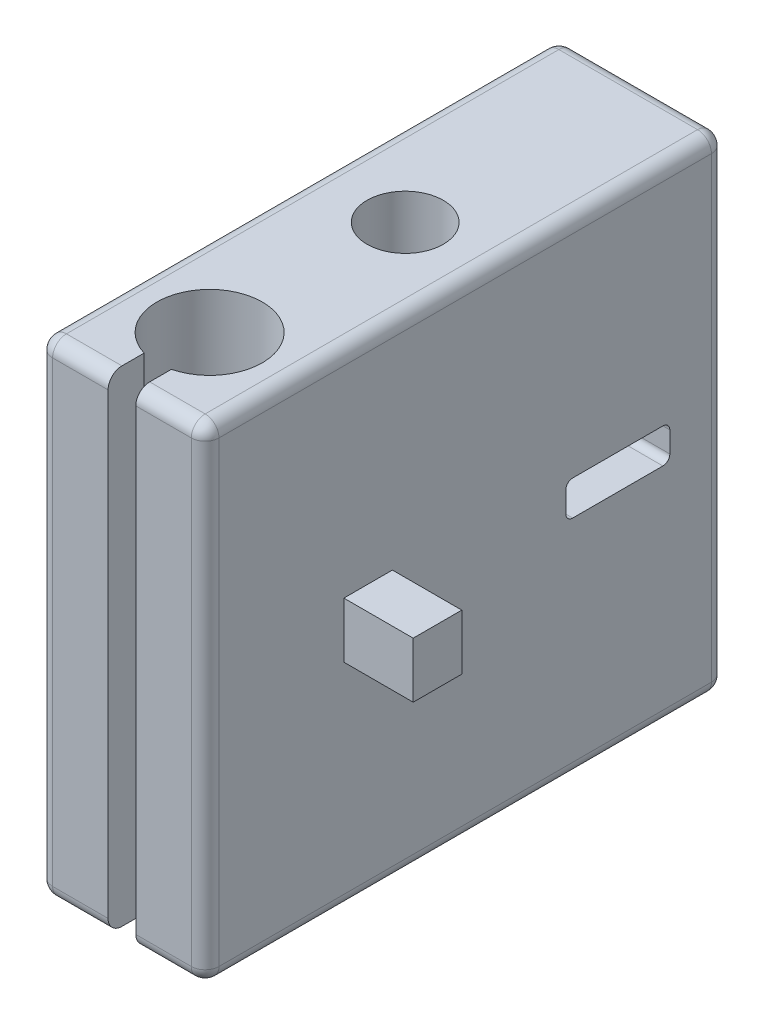
SolidWorks part; units mm, degrees
ref_plane "Front Plane" through (0, 0, 0) normal (0, 0, 1) x (1, 0, 0)
ref_plane "Top Plane" through (0, 0, 0) normal (0, 1, 0) x (1, 0, 0)
ref_plane "Right Plane" through (0, 0, 0) normal (1, 0, 0) x (0, 0, -1)
ref_plane "Plano1" through (-220, 0, 0) normal (1, 0, 0) x (0, 0, -1)
sketch "Esboço1" plane through (-220, 0, 0) normal (1, 0, 0) x (0, 0, -1)
  line L0 (-460.4999, 246.154) -> (-460.4999, 230.354) construction
  line L1 (-465.4999, 248.254) -> (-390.4999, 248.254)
  line L2 (-465.4999, 248.254) -> (-465.4999, 178.254)
  line L3 (-465.4999, 178.254) -> (-390.4999, 178.254)
  line L4 (-390.4999, 248.254) -> (-390.4999, 178.254)
  dimension "D1" = 75
  dimension "D2" = 70
  dimension "D3" = 5
extrude "Ressalto-extrusão1" add sketch "Esboço1" along normal blind 12 and the other way blind 12
sketch "Esboço3" plane through (0, 248.254, 0) normal (0, 1, 0) x (1, 0, 0)
  line L5 (-232, -465.4999) -> (-208, -465.4999) construction
  line L7 (-220, -465.4999) -> (-218, -465.4999)
  line L10 (-218, -465.4999) -> (-218, -460.3692)
  line L11 (-220, -465.4999) -> (-222, -465.4999)
  line L14 (-222, -465.4999) -> (-222, -460.292)
  arc A3 (-218, -460.3692) -> (-222, -460.292) centre (-219.8586, -452.9999) ccw
  circle A8 centre (-219.5085, -425.1499) radius 5.5
  circle A9 centre (-219.5085, -425.1499) radius 5.5
  dimension "D1" = 15.2
  dimension "D3" = 2
  dimension "D4" = 2
  dimension "D2" = 0.5
extrude "Corte-extrusão1" cut sketch "Esboço3" against normal through all
sketch "Esboço4" plane through (0, 0, 390.4999) normal (0, 0, -1) x (-1, 0, 0)
  line L0 (220, 248.254) -> (220, 178.254) construction
  line L1 (232, 248.254) -> (208, 248.254) construction
  line L2 (232, 178.254) -> (208, 178.254) construction
  circle A0 centre (219.8586, 238.254) radius 4.1
  circle A1 centre (219.8586, 188.254) radius 4.1
  dimension "D1" = 8.2
  dimension "D2" = 8.2
extrude "Corte-extrusão2" cut sketch "Esboço4" against normal blind 20
fillet "Filete1" radius 2 14 edges at (-227, 178.254, 465.4999) (-213, 178.254, 465.4999) (-213, 248.254, 465.4999) (-227, 248.254, 465.4999) (-208, 178.254, 427.9999) (-208, 248.254, 427.9999) (-208, 213.254, 465.4999) (-232, 178.254, 427.9999) (-232, 213.254, 465.4999) (-232, 248.254, 427.9999) (-220, 248.254, 390.4999) (-220, 178.254, 390.4999) (-208, 213.254, 390.4999) (-232, 213.254, 390.4999)
sketch "Esboço5" plane through (0, 0, 390.4999) normal (0, 0, -1) x (-1, 0, 0)
  line L8 (214.0299, 195.2585) -> (226.0299, 195.2486)
  line L9 (226.0299, 195.2486) -> (226.0594, 231.2486)
  line L10 (226.0594, 231.2486) -> (214.0594, 231.2584)
  line L11 (214.0594, 231.2584) -> (214.0299, 195.2585)
  line L12 (214.0299, 195.2585) -> (226.0299, 195.2486)
  line L13 (226.0299, 195.2486) -> (226.0594, 231.2486)
  line L14 (226.0594, 231.2486) -> (214.0594, 231.2584)
  line L15 (214.0594, 231.2584) -> (214.0299, 195.2585)
  dimension "D1" = 0
extrude "Corte-extrusão3" cut sketch "Esboço5" against normal blind 29
sketch "Esboço6" plane through (-232, 0, 0) normal (-1, 0, 0) x (0, 0, 1)
  line L0 (392.4999, 213.254) -> (463.4999, 213.254) construction
  line L1 (392.4999, 246.254) -> (392.4999, 180.254) construction
  line L2 (463.4999, 180.254) -> (463.4999, 246.254) construction
  line L3 (398.4999, 213.254) -> (413.4999, 213.254) construction
  line L4 (399.4999, 215.754) -> (412.4999, 215.754)
  line L5 (398.4999, 214.754) -> (398.4999, 211.754)
  line L6 (399.4999, 210.754) -> (412.4999, 210.754)
  line L7 (413.4999, 214.754) -> (413.4999, 211.754)
  arc A0 (412.4999, 215.754) -> (413.4999, 214.754) centre (412.4999, 214.754) cw
  arc A1 (412.4999, 210.754) -> (413.4999, 211.754) centre (412.4999, 211.754) ccw
  arc A2 (398.4999, 211.754) -> (399.4999, 210.754) centre (399.4999, 211.754) ccw
  arc A3 (399.4999, 215.754) -> (398.4999, 214.754) centre (399.4999, 214.754) ccw
  point P14 (413.4999, 215.754)
  point P17 (413.4999, 210.754)
  point P22 (398.4999, 215.754)
  dimension "D4" = 1
  dimension "D1" = 5
  dimension "D2" = 15
  dimension "D3" = 6
extrude "Corte-extrusão4" cut sketch "Esboço6" against normal blind 28
sketch "Esboço7" plane through (-208, 0, 0) normal (1, 0, 0) x (0, 0, -1)
  line L0 (-463.4999, 246.254) -> (-463.4999, 180.254) construction
  line L1 (-445.4999, 217.254) -> (-438.4999, 217.254)
  line L2 (-445.4999, 217.254) -> (-445.4999, 209.254)
  line L3 (-445.4999, 209.254) -> (-438.4999, 209.254)
  line L4 (-438.4999, 217.254) -> (-438.4999, 209.254)
  line L5 (-465.4999, 180.254) -> (-465.4999, 246.254) construction
  point P6 (-463.4999, 213.254)
  point P7 (-445.4999, 213.254)
  dimension "D1" = 7
  dimension "D2" = 8
  dimension "D3" = 20
extrude "Ressalto-extrusão2" add sketch "Esboço7" along normal blind 10 and the other way blind 34
ref_point "Ponto1"
